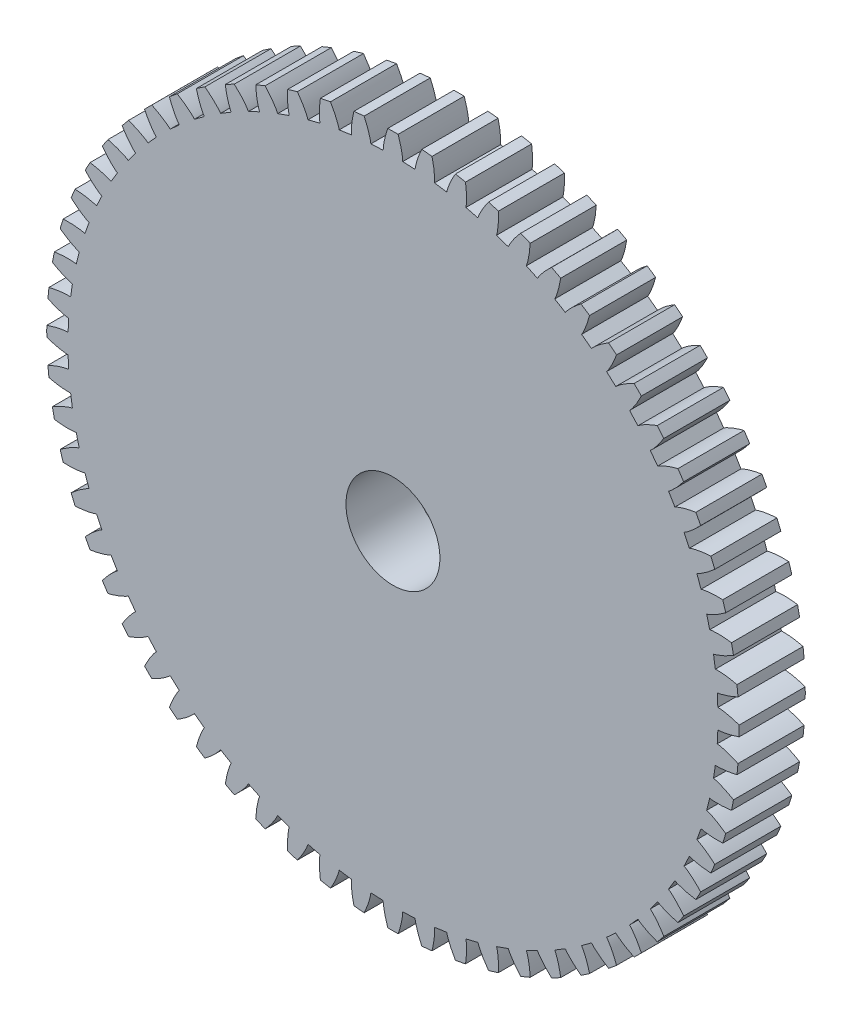
SolidWorks part; units mm, degrees
material "Plain Carbon Steel"
ref_plane "Front Plane" through (0, 0, 0) normal (0, 0, 1) x (1, 0, 0)
ref_plane "Top Plane" through (0, 0, 0) normal (0, 1, 0) x (1, 0, 0)
ref_plane "Right Plane" through (0, 0, 0) normal (1, 0, 0) x (0, 0, -1)
sketch "Sketch1" plane through (0, 0, 0) normal (0, 0, 1) x (1, 0, 0)
  circle A0 centre (0, 0) radius 52.3875
  dimension "D1" = 104.775
extrude "Boss-Extrude1" add sketch "Sketch1" along normal blind 10
sketch "Sketch2" plane through (0, 0, 0) normal (0, 0, 1) x (1, 0, 0)
  spline S0 degree 4 poles (49.1596, 1.4796) (49.1645, 1.4797) (49.1783, 1.4799) (49.2042, 1.4798) (49.2467, 1.4789) (49.3008, 1.4769) (49.3708, 1.4732) (49.4534, 1.4673) (49.5443, 1.4594) (49.6433, 1.4491) (49.7422, 1.4374) (49.841, 1.4244) (49.9396, 1.4103) (50.0592, 1.3917) (50.2028, 1.3674) (50.371, 1.3361) (50.5622, 1.2971) (50.7575, 1.2536) (50.9501, 1.2078) (51.1452, 1.158) (51.3344, 1.1072) (51.5315, 1.0509) (51.7136, 0.9971) (51.9184, 0.9327) (52.0839, 0.8796) (52.3029, 0.8051) (52.4325, 0.7599) (52.5844, 0.7054) (52.652, 0.6804) (52.6936, 0.6651) knots 0 0 0 0 0 0.005377 0.015084 0.028532 0.04661 0.064855 0.092111 0.119476 0.146842 0.174209 0.201575 0.228941 0.256307 0.307035 0.361767 0.4165 0.471232 0.525964 0.580697 0.635429 0.690161 0.744894 0.799626 0.854358 0.909091 0.954545 1 1 1 1 1 construction
  spline S1 degree 4 poles (49.1596, 1.4796) (49.1645, 1.4797) (49.1783, 1.4799) (49.2042, 1.4798) (49.2467, 1.4789) (49.3008, 1.4769) (49.3708, 1.4732) (49.4534, 1.4673) (49.5443, 1.4594) (49.6433, 1.4491) (49.7422, 1.4374) (49.841, 1.4244) (49.9396, 1.4103) (50.0592, 1.3917) (50.2028, 1.3674) (50.371, 1.3361) (50.5622, 1.2971) (50.7575, 1.2536) (50.9501, 1.2078) (51.1452, 1.158) (51.3344, 1.1072) (51.5315, 1.0509) (51.7136, 0.9971) (51.9184, 0.9327) (52.0839, 0.8796) (52.2554, 0.8213) (52.339, 0.7924) (52.3817, 0.7774) knots 0 0 0 0 0 0.005377 0.015084 0.028532 0.04661 0.064855 0.092111 0.119476 0.146842 0.174209 0.201575 0.228941 0.256307 0.307035 0.361767 0.4165 0.471232 0.525964 0.580697 0.635429 0.690161 0.744894 0.799626 0.854358 0.909091 0.909091 0.909091 0.909091 0.909091
  spline S2 degree 4 poles (49.0679, 3.346) (49.0728, 3.3464) (49.0865, 3.3476) (49.1123, 3.3502) (49.1545, 3.3552) (49.2081, 3.3625) (49.2774, 3.3731) (49.3591, 3.387) (49.4487, 3.4038) (49.5463, 3.4238) (49.6436, 3.4451) (49.7407, 3.4677) (49.8374, 3.4915) (49.9546, 3.5217) (50.0951, 3.5599) (50.2594, 3.6076) (50.4458, 3.6651) (50.6359, 3.7275) (50.8232, 3.792) (51.0125, 3.8607) (51.1957, 3.9297) (51.3863, 4.0051) (51.5624, 4.0765) (51.7599, 4.1607) (51.9193, 4.2298) (52.13, 4.3253) (52.2545, 4.3831) (52.4003, 4.4522) (52.4652, 4.4836) (52.5051, 4.503) knots 0 0 0 0 0 0.005377 0.015084 0.028532 0.04661 0.064855 0.092111 0.119476 0.146842 0.174209 0.201575 0.228941 0.256307 0.307035 0.361767 0.4165 0.471232 0.525964 0.580697 0.635429 0.690161 0.744894 0.799626 0.854358 0.909091 0.954545 1 1 1 1 1 construction
  spline S3 degree 4 poles (49.0679, 3.346) (49.0728, 3.3464) (49.0865, 3.3476) (49.1123, 3.3502) (49.1545, 3.3552) (49.2081, 3.3625) (49.2774, 3.3731) (49.3591, 3.387) (49.4487, 3.4038) (49.5463, 3.4238) (49.6436, 3.4451) (49.7407, 3.4677) (49.8374, 3.4915) (49.9546, 3.5217) (50.0951, 3.5599) (50.2594, 3.6076) (50.4458, 3.6651) (50.6359, 3.7275) (50.8232, 3.792) (51.0125, 3.8607) (51.1957, 3.9297) (51.3863, 4.0051) (51.5624, 4.0765) (51.7599, 4.1607) (51.9193, 4.2298) (52.0843, 4.3046) (52.1646, 4.3415) (52.2057, 4.3606) knots 0 0 0 0 0 0.005377 0.015084 0.028532 0.04661 0.064855 0.092111 0.119476 0.146842 0.174209 0.201575 0.228941 0.256307 0.307035 0.361767 0.4165 0.471232 0.525964 0.580697 0.635429 0.690161 0.744894 0.799626 0.854358 0.909091 0.909091 0.909091 0.909091 0.909091
  spline S4 degree 1 poles (49.0679, 3.346) (49.1596, 1.4796) knots 0 0 1 1 construction
  spline S5 degree 1 poles (49.0679, 3.346) (49.1596, 1.4796) knots 0 0 1 1
  spline S6 degree 1 poles (52.3817, 0.7774) (59.9934, 0.8904) knots 0 0 1 1 construction
  spline S7 degree 1 poles (52.3817, 0.7774) (59.9934, 0.8904) knots 0 0 1 1
  spline S8 degree 4 poles (59.9981, 0.4767) (59.9979, 0.5063) (59.9973, 0.5633) (59.9967, 0.6404) (59.9941, 0.8495) (59.9927, 0.941) (59.9881, 1.2106) (59.9845, 1.3636) (59.9793, 1.5848) (59.9741, 1.765) (59.9679, 1.9699) (59.9612, 2.1599) (59.9538, 2.3588) (59.9458, 2.5524) (59.9372, 2.7489) (59.9278, 2.9441) (59.918, 3.1392) (59.9073, 3.3356) (59.8963, 3.5291) (59.8842, 3.7277) (59.8722, 3.9174) (59.8583, 4.122) (59.8458, 4.3018) (59.8293, 4.5225) (59.8179, 4.6751) (59.7961, 4.9439) (59.7884, 5.0351) (59.7706, 5.2434) (59.7637, 5.3202) (59.7586, 5.377) (59.7559, 5.4064) knots 0 0 0 0 0 0.020959 0.041918 0.083333 0.123016 0.162698 0.202381 0.242063 0.281746 0.321429 0.361111 0.400794 0.440476 0.480159 0.519841 0.559524 0.599206 0.638889 0.678571 0.718254 0.757937 0.797619 0.837302 0.876984 0.916667 0.958082 0.979041 1 1 1 1 1 construction
  spline S9 degree 4 poles (59.9934, 0.8904) (59.9928, 0.9312) (59.9915, 1.0106) (59.9881, 1.2106) (59.9845, 1.3636) (59.9793, 1.5848) (59.9741, 1.765) (59.9679, 1.9699) (59.9612, 2.1599) (59.9538, 2.3588) (59.9458, 2.5524) (59.9372, 2.7489) (59.9278, 2.9441) (59.918, 3.1392) (59.9073, 3.3356) (59.8963, 3.5291) (59.8842, 3.7277) (59.8722, 3.9174) (59.8583, 4.122) (59.8458, 4.3018) (59.8293, 4.5225) (59.8179, 4.6751) (59.8017, 4.8745) (59.7952, 4.9536) (59.7918, 4.9943) knots 0.083333 0.083333 0.083333 0.083333 0.083333 0.123016 0.162698 0.202381 0.242063 0.281746 0.321429 0.361111 0.400794 0.440476 0.480159 0.519841 0.559524 0.599206 0.638889 0.678571 0.718254 0.757937 0.797619 0.837302 0.876984 0.916667 0.916667 0.916667 0.916667 0.916667
  spline S10 degree 1 poles (59.7918, 4.9943) (52.2057, 4.3606) knots 0 0 1 1 construction
  spline S11 degree 1 poles (59.7918, 4.9943) (52.2057, 4.3606) knots 0 0 1 1
extrude "Cut-Extrude2" cut sketch "Sketch2" against normal blind 11 and the other way blind 11
ref_axis "Axis1" through (0, 0, -0.5) along (0, 0, 1)
pattern_circular "CirPattern1" count 64 over 360 about axis through (0, 0, -0.5) along (0, 0, 1) of "Cut-Extrude2"
sketch "Sketch3" plane through (0, 0, 0) normal (0, 0, 1) x (1, 0, 0)
  circle A0 centre (0, 0) radius 7.112
  dimension "D1" = 14.224
extrude "Cut-Extrude4" cut sketch "Sketch3" against normal blind 12 and the other way blind 12
